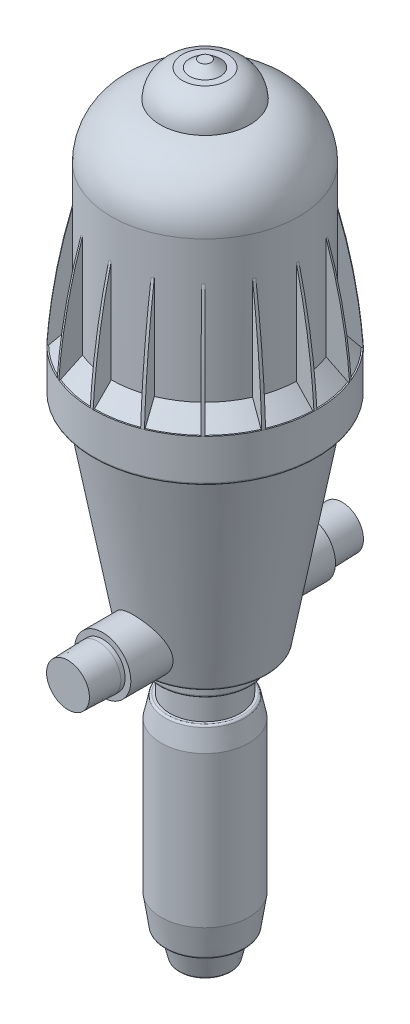
SolidWorks part; units mm, degrees
ref_plane "Front Plane" through (0, 0, 0) normal (0, 0, 1) x (1, 0, 0)
ref_plane "Top Plane" through (0, 0, 0) normal (0, 1, 0) x (1, 0, 0)
ref_plane "Right Plane" through (0, 0, 0) normal (1, 0, 0) x (0, 0, -1)
sketch "Sketch1" plane through (0, 0, 0) normal (0, 0, 1) x (1, 0, 0)
  line L0 (0, 65.4467) -> (0, -350.6816) construction
  line L1 (0, 65.4467) -> (55.88, 65.4467) construction
  line L2 (55.88, 65.4467) -> (55.88, -51.5533)
  line L3 (65.88, -61.5533) -> (55.88, -51.5533)
  line L4 (66.675, -61.5533) -> (65.88, -61.5533)
  line L5 (66.675, -61.5533) -> (66.675, -86.9533)
  line L6 (66.675, -86.9533) -> (0, -86.9533) construction
  line L7 (59.436, -86.9533) -> (66.675, -86.9533)
  line L8 (59.436, -86.9533) -> (36.5125, -213.9533)
  line L9 (36.5125, -213.9533) -> (0, -213.9533) construction
  line L10 (27.051, -213.9533) -> (27.051, -224.6213)
  line L11 (20.955, -241.1313) -> (23.495, -241.1313)
  line L12 (0, -253.8313) -> (26.162, -253.8313) construction
  line L13 (0, -224.6213) -> (20.955, -224.6213) construction
  line L14 (27.051, -213.9533) -> (36.5125, -213.9533)
  line L15 (0, -241.1313) -> (20.955, -241.1313) construction
  line L16 (20.955, -224.6213) -> (20.955, -241.1313)
  line L17 (0, -241.1313) -> (23.495, -241.1313) construction
  line L18 (0, -241.1313) -> (0, -361.7813) construction
  line L19 (0, -361.7813) -> (23.495, -361.7813) construction
  line L20 (23.495, -241.1313) -> (23.495, -361.7813) construction
  line L21 (0, -343.7473) -> (26.162, -343.7473) construction
  line L22 (23.495, -241.1313) -> (26.162, -253.8313)
  line L23 (26.162, -253.8313) -> (26.162, -343.7473)
  line L24 (26.162, -343.7473) -> (23.495, -361.7813)
  line L25 (19.304, -361.7813) -> (23.495, -361.7813)
  line L26 (0, -361.7813) -> (19.304, -361.7813) construction
  line L27 (0, -350.6816) -> (0, -397.4894) construction
  line L28 (0, -377.7833) -> (15.24, -377.7833)
  line L29 (19.304, -361.7813) -> (15.24, -377.7833)
  line L30 (20.955, -224.6213) -> (27.051, -224.6213)
  line L31 (0, 86.0207) -> (0, -377.7833)
  line L32 (26.67, 65.4467) -> (55.88, 65.4467)
  line L33 (0, 86.0207) -> (9.144, 86.0207) construction
  line L34 (9.144, 86.0207) -> (9.144, 81.7027) construction
  line L35 (9.144, 81.7027) -> (26.67, 81.7027) construction
  line L36 (26.67, 81.7027) -> (26.67, 65.4467) construction
  line L37 (9.144, 81.7027) -> (13.5032, 81.7027)
  line L38 (3.5482, 86.0207) -> (9.144, 81.7027)
  line L39 (3.5482, 86.0207) -> (0, 86.0207)
  spline S0 degree 2 poles (13.5032, 81.7027) (25.6768, 78.3249) (26.67, 65.4467) knots 0 0 0 1 1 1
  point P3 (55.88, -61.5533)
  dimension "D1" = 55.88
  dimension "D2" = 127
  dimension "D3" = 66.675
  dimension "D4" = 25.4
  dimension "D5" = 59.436
  dimension "D6" = 36.5125
  dimension "D8" = 127
  dimension "D9" = 27.051
  dimension "D10" = 10.668
  dimension "D11" = 20.955
  dimension "D12" = 16.51
  dimension "D13" = 23.495
  dimension "D14" = 120.65
  dimension "D15" = 26.162
  dimension "D16" = 12.7
  dimension "D17" = 18.034
  dimension "D18" = 19.304
  dimension "D19" = 16.256
  dimension "D20" = 15.24
  dimension "D21" = 16.002
  dimension "D22" = 4.318
  dimension "D23" = 9.144
  dimension "D24" = 26.67
revolve "Revolve1" add sketch "Sketch1" angle 360 about L31
fillet "Fillet1" radius 33.02 1 edges at (-55.88, 65.4467, 0)
ref_axis "Axis1" through (0, -51.5533, 0) along (0, 1, 0)
sketch "Sketch2" plane through (0, 0, 0) normal (0, 0, 1) x (1, 0, 0)
  line L0 (66.675, -61.5533) -> (-66.675, -61.5533) construction
  line L1 (-66.675, -61.5533) -> (-55.88, -61.5533) construction
  line L2 (-66.675, -61.5533) -> (-66.675, 9.5667) construction
  line L3 (-66.675, 9.5667) -> (-55.88, 9.5667) construction
  line L4 (-55.88, -61.5533) -> (-55.88, 9.5667) construction
  line L5 (-55.88, 32.6472) -> (-55.88, -51.5533) construction
  line L6 (-66.675, -61.5533) -> (-65.88, -61.5533)
  line L7 (-55.88, -51.5533) -> (-65.88, -61.5533) construction
  line L8 (-65.88, -61.5533) -> (-55.88, -51.5533)
  line L9 (-55.88, -51.5533) -> (-55.88, 9.5667)
  line L10 (0, 86.0207) -> (0, -398.3691) construction
  line L11 (3.5482, 86.0207) -> (-3.5482, 86.0207) construction
  spline S0 degree 2 poles (-55.88, 9.5667) (-64.5076, -25.5351) (-66.675, -61.5533) knots 0 0 0 1 1 1
  dimension "D1" = 71.12
revolve "Revolve2" add sketch "Sketch2" angle 1.5 about L10
pattern_circular "CirPattern1" count 16 over 360 about axis through (0, -51.5533, 0) along (0, 1, 0) of "Revolve2"
fillet "Fillet3" radius 1.27 7 edges at (-23.495, -241.1313, 0) (-27.051, -213.9533, 0) (-27.051, -224.6213, 0) (-36.5125, -213.9533, 0) (-66.675, -86.9533, 0) (-15.24, -377.7833, 0) (-23.495, -361.7813, 0)
sketch "Sketch3" plane through (0, 0, 0) normal (0, 0, 1) x (1, 0, 0)
  line L0 (36.701, -212.9089) -> (-36.701, -212.9089) construction
  circle A0 centre (0, -196.1449) radius 16.764
  dimension "D1" = 33.528
extrude "Boss-Extrude1" add sketch "Sketch3" along normal blind 60.96 and the other way blind 60.96
sketch "Sketch6" plane through (0, 0, 0) normal (1, 0, 0) x (0, 0, -1)
  line L0 (-60.96, -196.1449) -> (-81.6429, -196.1449)
  line L1 (-60.96, -179.3809) -> (-60.96, -212.9089) construction
  line L2 (-81.6429, -196.1449) -> (-81.6429, -183.3769)
  line L3 (-81.6429, -183.3769) -> (-63.5, -182.8099)
  line L4 (-63.5, -182.8099) -> (-60.96, -182.8099)
  line L5 (-60.96, -182.8099) -> (-60.96, -196.1449)
  point P6 (-60.96, -182.8099)
  point P8 (0, 0)
  point P9 (0, 0)
  dimension "D1" = 13.335
  dimension "D2" = 1.79
  dimension "D3" = 18.1429
revolve "Revolve3" add sketch "Sketch6" angle 360 about L0
sketch "Sketch8" plane through (0, 0, 0) normal (1, 0, 0) x (0, 0, -1)
  line L0 (-63.5, -196.1449) -> (-81.6429, -196.1449) construction
  line L1 (-63.5, -182.8099) -> (-63.5, -209.4799) construction
  line L2 (-81.6429, -183.3769) -> (-81.6429, -208.913) construction
  line L3 (-81.6429, -182.9873) -> (-82.5423, -184.6641) construction
  line L6 (-82.5423, -184.6641) -> (-83.5447, -183.0467) construction
  line L7 (-83.5447, -183.0467) -> (-81.6429, -182.9873)
  line L8 (-83.5447, -183.0467) -> (-82.6618, -184.4712)
  line L9 (-82.6618, -184.4712) -> (-82.4351, -184.4641)
  line L10 (-82.4351, -184.4641) -> (-81.6429, -182.9873)
  point P9 (-83.0435, -183.8554)
  dimension "D1" = 12.2895
  dimension "D3" = 60
  dimension "D4" = 1.4514
  dimension "D6" = 1.79
sketch "Sketch4" plane through (0, 0, 60.96) normal (0, 0, 1) x (1, 0, 0)
  circle A0 centre (0, -196.1449) radius 13.208
  dimension "D1" = 26.416
sketch "Sketch9" plane through (0, 0, 81.6429) normal (0, 0, 1) x (1, 0, 0)
  circle A1 centre (0, -196.1449) radius 12.768
  circle A2 centre (0, -196.1449) radius 12.768
  dimension "D1" = 0
curve "Helix/Spiral1"
extrude "Boss-Extrude2" add sketch "Sketch4" along normal blind 19.05 draft 2
mirror "Mirror1" about plane through (0, 0, 0) normal (0, 0, 1) of "Revolve3"
equation "\"D2@Sketch6\"=atn(1/32)"
equation "\"D2@Sketch8\"=(1/14)/8"
equation "\"D6@Sketch8\"=atn(1/32)"
